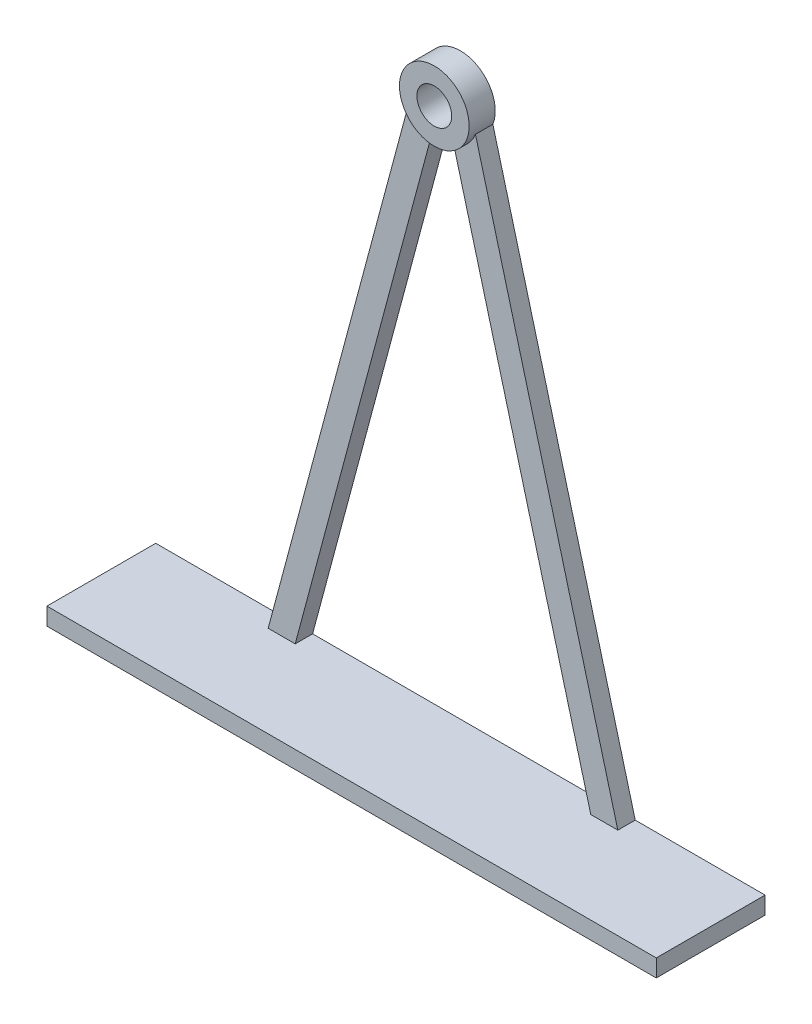
SolidWorks part; units mm, degrees
ref_plane "前视基准面" through (0, 0, 0) normal (0, 0, 1) x (1, 0, 0)
ref_plane "上视基准面" through (0, 0, 0) normal (0, 1, 0) x (1, 0, 0)
ref_plane "右视基准面" through (0, 0, 0) normal (1, 0, 0) x (0, 0, -1)
other "Configuration Table"
sketch "草图3" plane through (0, 0, 0) normal (0, 0, 1) x (1, 0, 0)
  circle A2 centre (0, 0) radius 8
  circle A3 centre (0, 0) radius 4
  dimension "D2" = 16
  dimension "D3" = 8
extrude "凸台-拉伸-转轴" add sketch "草图3" along normal blind 6
sketch "草图6" plane through (0, 0, 0) normal (0, 0, 1) x (1, 0, 0)
  line L2 (-33.9574, -125) -> (-2.5, -7.5993)
  line L4 (-40.1691, -125) -> (-33.9574, -125)
  line L5 (-40.1691, -125) -> (-7.4539, -2.9052)
  line L6 (0, 0) -> (0, -125) construction
  line L7 (0, -125) -> (-33.9574, -125) construction
  circle A0 centre (0, 0) radius 8 construction
  circle A1 centre (0, 0) radius 8
  dimension "D1" = 6
  dimension "D4" = 125
  dimension "D5" = 75
  dimension "D7" = 5
extrude "凸台-拉伸-支脚" add sketch "草图6" along normal offset from surface (4 mm away) 2 contours A1 L5 L4 L2 region at (-21.1135, -65.4014, 0) up to face at (8, 0, 6)
mirror "镜向-支脚" about plane through (0, 0, 0) normal (1, 0, 0) of "凸台-拉伸-支脚"
sketch "草图7" plane through (0, -125, 0) normal (0, -1, 0) x (1, 0, 0)
  line L0 (-70, 25) -> (70, 25)
  line L1 (70, 25) -> (70, 0)
  line L2 (70, 0) -> (-70, 0)
  line L3 (-70, 0) -> (-70, 25)
  line L4 (0, 0) -> (0, 25) construction
  dimension "D1" = 140
  dimension "D2" = 25
extrude "凸台-拉伸-底座" add sketch "草图7" along normal blind 4
